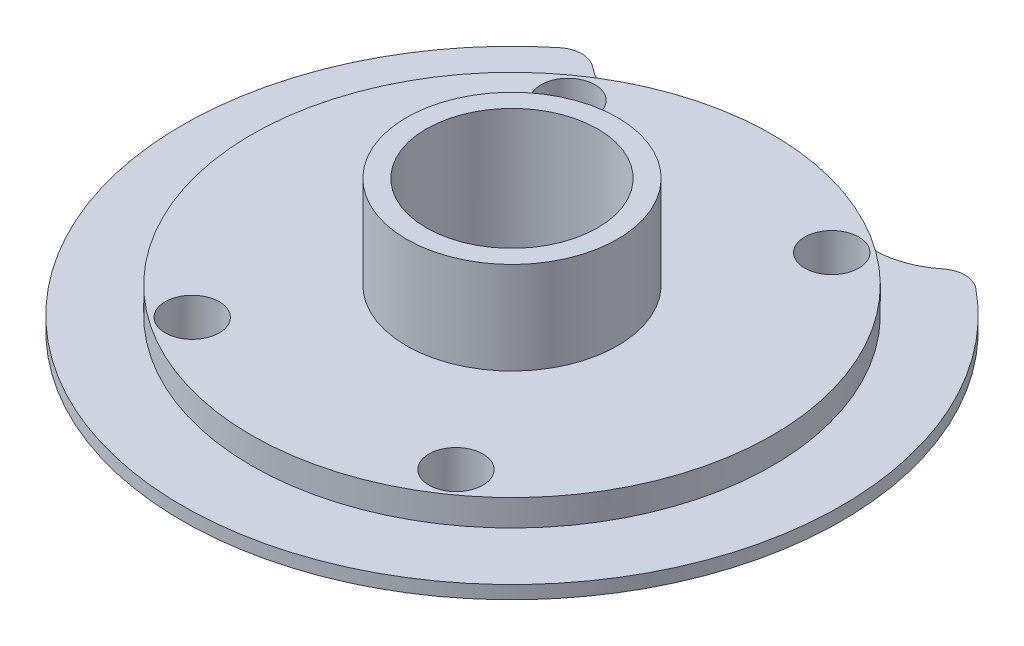
SolidWorks part; units mm, degrees
ref_plane "Front Plane" through (0, 0, 0) normal (0, 0, 1) x (1, 0, 0)
ref_plane "Top Plane" through (0, 0, 0) normal (0, 1, 0) x (1, 0, 0)
ref_plane "Right Plane" through (0, 0, 0) normal (1, 0, 0) x (0, 0, -1)
sketch "Sketch1" plane through (0, 0, 0) normal (0, 1, 0) x (1, 0, 0)
  circle A4 centre (0, 0) radius 12.5
  dimension "D1" = 25
extrude "Boss-Extrude1" add sketch "Sketch1" along normal blind 1.5
sketch "Sketch2" plane through (0, 0, 0) normal (0, -1, 0) x (1, 0, 0)
  circle A0 centre (0, 0) radius 3.25
  dimension "D1" = 6.5
extrude "Cut-Extrude1" cut sketch "Sketch2" against normal through all
sketch "Sketch3" plane through (0, 1.5, 0) normal (0, 1, 0) x (1, 0, 0)
  circle A0 centre (0, 0) radius 3.25 construction
  circle A1 centre (0, 0) radius 12.5
  circle A2 centre (0, 0) radius 12.5
  circle A3 centre (0, 0) radius 3.25
  circle A4 centre (0, 0) radius 4
  circle M4 centre (0, 0) radius 3.25
  dimension "D1" = 0
  dimension "D2" = 0.75
extrude "Boss-Extrude2" add sketch "Sketch3" along normal blind 3.5 contours A4 M4 region at (-3.8869, 1.5, 0)
sketch "Sketch4" plane through (0, 1.5, 0) normal (0, 1, 0) x (1, 0, 0)
  circle A0 centre (0, 0) radius 12.5 construction
  circle A1 centre (0, 0) radius 12.5
  circle A2 centre (0, 0) radius 9.875
  circle M4 centre (0, 0) radius 12.5
  dimension "D1" = 19.75
extrude "Cut-Extrude2" cut sketch "Sketch4" against normal blind 1 contours A2 M4 region at (-12.1464, 1.5, 0)
sketch "Sketch5" plane through (0, 0.5, 0) normal (0, 1, 0) x (1, 0, 0)
  line L0 (0, 0) -> (7.1697, 10.2394)
  line L1 (0, 0) -> (0, 12.5) construction
  line L2 (0, 0) -> (-7.1697, 10.2394)
  circle A0 centre (0, 0) radius 9.875 construction
  circle A1 centre (0, 0) radius 12.5
  circle A2 centre (0, 0) radius 12.5
  circle A3 centre (0, 0) radius 9.875
  circle M4 centre (0, 0) radius 9.875
  circle M5 centre (0, 0) radius 12.5
  dimension "D2" = 35
  dimension "D1" = 0
extrude "Cut-Extrude3" cut sketch "Sketch5" against normal through all contours L1 A3 L0 M5 | L1 A2 L2 M4 region at (3.3273, 0.5, -10.5528) region at (-3.3273, 0.5, -10.5528)
fillet "Fillet1" radius 3.125 2 edges at (-5.6641, 0.25, -8.0891) (5.6641, 0.25, -8.0891)
fillet "Fillet2" radius 1 2 edges at (-7.1697, 0.25, -10.2394) (7.1697, 0.25, -10.2394)
sketch "Sketch6" plane through (0, 0, 0) normal (0, -1, 0) x (1, 0, 0)
  line L0 (0, 0) -> (5, 0) construction
  line L1 (-5, -7.125) -> (5, -7.125) construction
  line L2 (-5, -7.125) -> (-5, 7.125) construction
  line L3 (-5, 7.125) -> (5, 7.125) construction
  line L4 (5, -7.125) -> (5, 7.125) construction
  line L5 (-5, -7.125) -> (5, 7.125) construction
  line L6 (-5, 7.125) -> (5, -7.125) construction
  line L7 (0, 0) -> (0, 7.125) construction
  circle A0 centre (5, 7.125) radius 1.025
  circle A1 centre (-5, 7.125) radius 1.025
  circle A2 centre (5, -7.125) radius 1.025
  circle A3 centre (-5, -7.125) radius 1.025
  point P0 (0, 0)
  dimension "D3" = 2.05
  dimension "D1" = 10
  dimension "D2" = 14.25
extrude "Cut-Extrude4" cut sketch "Sketch6" against normal through all contours A1 | A0 | A2 | A3 region at (5, 0, 7.125) region at (-5, 0, 7.125) region at (5, 0, -7.125) region at (-5, 0, -7.125)
ref_plane "Plane1" through (0, 5, 0) normal (0, 1, 0) x (1, 0, 0)
ref_plane "Plane2" through (12.5, 0, 0) normal (1, 0, 0) x (0, 0, -1)
ref_axis "Axis1" through (12.5, 5, -10.7987) along (0, 0, 1)
ref_plane "Plane3" through (0, 0, -10) normal (0, 0, 1) x (1, 0, 0)
ref_point "MachiningOrigin"
